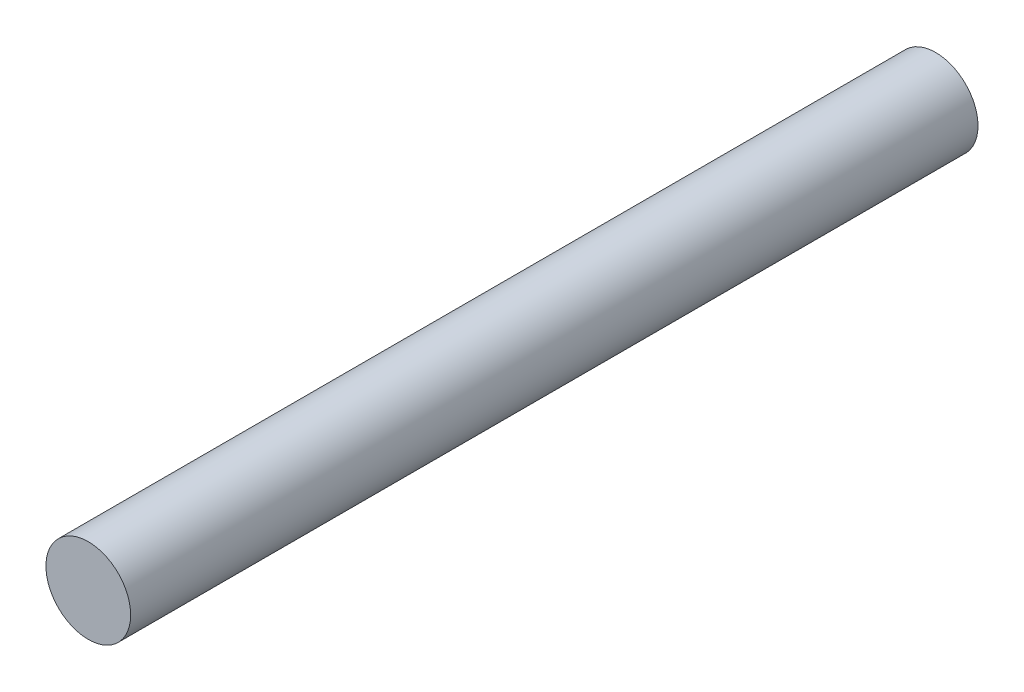
SolidWorks part; units mm, degrees
ref_plane "Front Plane" through (0, 0, 0) normal (0, 0, 1) x (1, 0, 0)
ref_plane "Top Plane" through (0, 0, 0) normal (0, 1, 0) x (1, 0, 0)
ref_plane "Right Plane" through (0, 0, 0) normal (1, 0, 0) x (0, 0, -1)
sketch "Sketch1" plane through (0, 0, 0) normal (0, 0, 1) x (1, 0, 0)
  circle A0 centre (0, 0) radius 3
  dimension "D1" = 6
extrude "Boss-Extrude1" add sketch "Sketch1" along normal blind 30 and the other way blind 30
